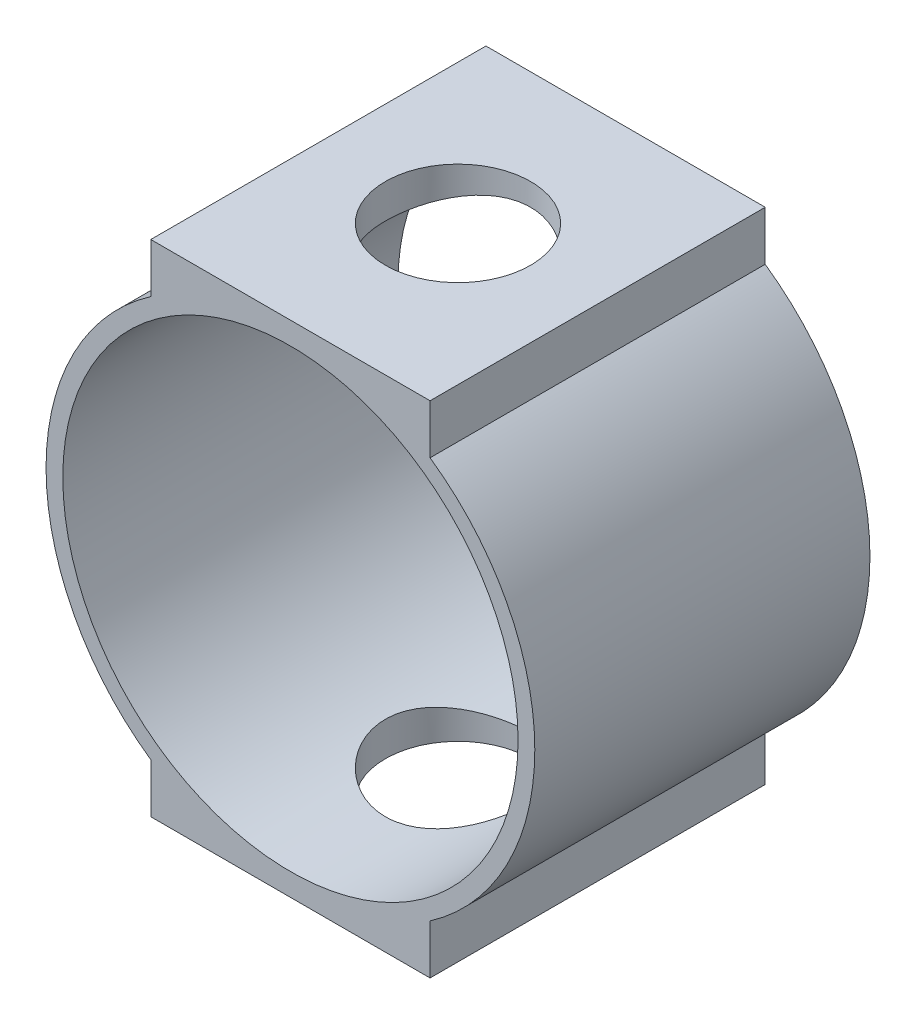
SolidWorks part; units mm, degrees
ref_plane "Front Plane" through (0, 0, 0) normal (0, 0, 1) x (1, 0, 0)
ref_plane "Top Plane" through (0, 0, 0) normal (0, 1, 0) x (1, 0, 0)
ref_plane "Right Plane" through (0, 0, 0) normal (1, 0, 0) x (0, 0, -1)
sketch "Sketch1" plane through (0, 0, 0) normal (0, 0, 1) x (1, 0, 0)
  line L0 (-5, 8.95) -> (5, 8.95)
  line L1 (5, 8.95) -> (5, 7.1807)
  line L2 (-5, 8.95) -> (-5, 7.1807)
  line L3 (0, 8.95) -> (0, 0) construction
  line L4 (0, 0) -> (-4.7286, 0) construction
  line L5 (5, -8.95) -> (5, -7.1807)
  line L6 (-5, -8.95) -> (5, -8.95)
  line L7 (-5, -8.95) -> (-5, -7.1807)
  circle A0 centre (0, 0) radius 8.15
  arc A1 (-5, 7.1807) -> (-5, -7.1807) centre (0, 0) ccw
  arc A2 (5, -7.1807) -> (5, 7.1807) centre (0, 0) ccw
  dimension "D1" = 16.3
  dimension "D2" = 0.6
  dimension "D4" = 0.8
  dimension "D3" = 10
extrude "Boss-Extrude2" add sketch "Sketch1" along normal blind 6 and the other way blind 6
sketch "Sketch2" plane through (0, 8.95, 0) normal (0, 1, 0) x (1, 0, 0)
  circle A0 centre (0, 0) radius 2.6
  dimension "D1" = 5.2
extrude "Cut-Extrude1" cut sketch "Sketch2" against normal through all
